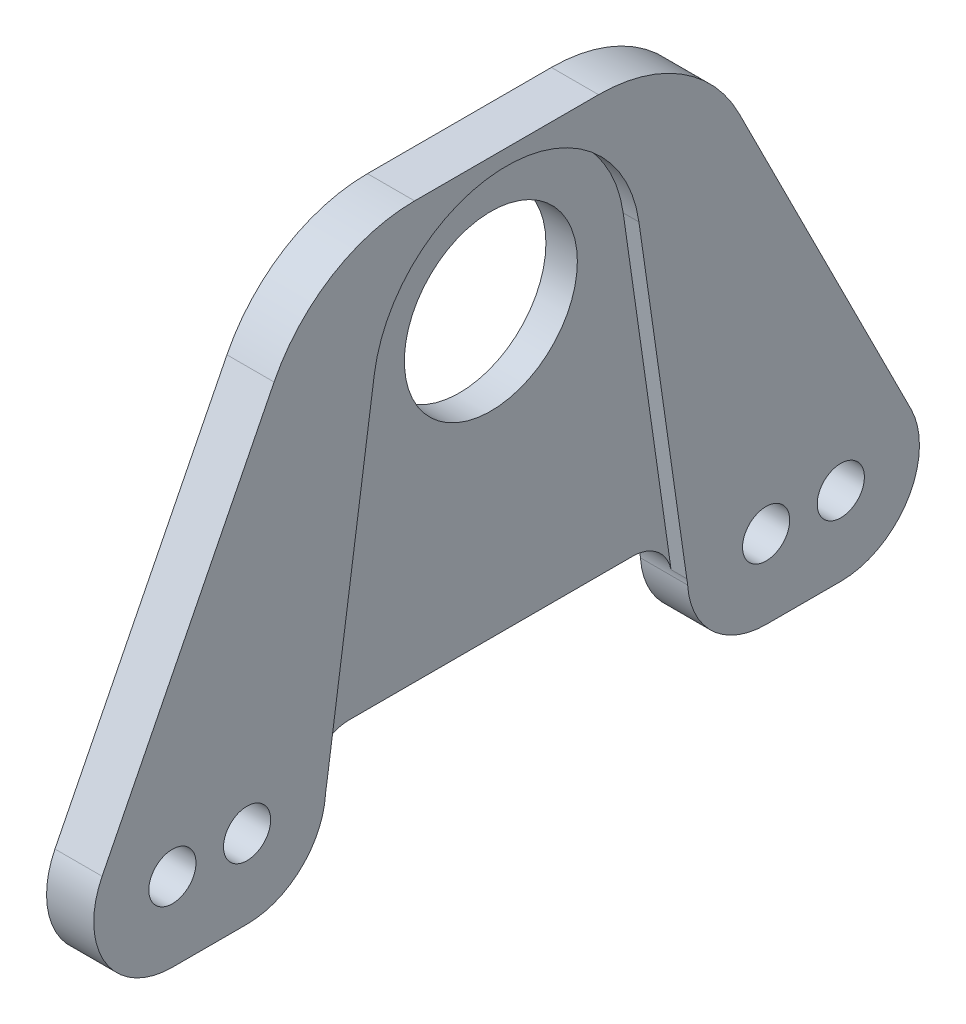
SolidWorks part; units mm, degrees
ref_plane "Front" through (0, 0, 0) normal (0, 0, 1) x (1, 0, 0)
ref_plane "Top" through (0, 0, 0) normal (0, 1, 0) x (1, 0, 0)
ref_plane "Right" through (0, 0, 0) normal (1, 0, 0) x (0, 0, -1)
sketch "Szkic2" plane through (0, 0, 0) normal (1, 0, 0) x (0, 0, -1)
  line L0 (-42.4983, -50) -> (-33, -50)
  line L1 (18.0334, -36) -> (-18.0334, -36)
  line L2 (42.4983, -50) -> (33, -50)
  line L3 (29.5637, 7.9846) -> (51.4325, -35.5077)
  line L4 (-29.5637, 7.9846) -> (-51.4325, -35.5077)
  line L5 (-11.6954, 19) -> (11.6954, 19)
  circle A0 centre (-42.4983, -40) radius 3
  circle A1 centre (-33, -40) radius 3
  arc A2 (-33, -50) -> (-23.0222, -40.6667) centre (-33, -40) ccw
  arc A3 (-51.4325, -35.5077) -> (-42.4983, -50) centre (-42.4983, -40) ccw
  arc A4 (-18.0334, -36) -> (-23.0222, -40.6667) centre (-18.0334, -41) ccw
  arc A5 (23.0222, -40.6667) -> (18.0334, -36) centre (18.0334, -41) ccw
  arc A6 (23.0222, -40.6667) -> (33, -50) centre (33, -40) ccw
  arc A7 (42.4983, -50) -> (51.4325, -35.5077) centre (42.4983, -40) ccw
  circle A8 centre (42.4983, -40) radius 3
  circle A9 centre (33, -40) radius 3
  arc A10 (-11.6954, 19) -> (-29.5637, 7.9846) centre (-11.6954, -1) ccw
  arc A11 (29.5637, 7.9846) -> (11.6954, 19) centre (11.6954, -1) ccw
  circle A12 centre (0, 0) radius 11
extrude "Dodanie-wyciągnięcie1" add sketch "Szkic2" along normal blind 6
sketch "Szkic3" plane through (6, 0, 0) normal (1, 0, 0) x (0, 0, -1)
  line L0 (-23.0222, -40.6667) -> (-16.8269, 2.4195)
  line L1 (23.0222, -40.6667) -> (16.8269, 2.4195)
  line L2 (-23.0222, -40.6667) -> (23.0222, -40.6667)
  arc A0 (16.8269, 2.4195) -> (-16.8269, 2.4195) centre (0, 0) ccw
  dimension "D1" = 34
extrude "Wytnij-wyciągnięcie1" cut sketch "Szkic3" against normal blind 2
